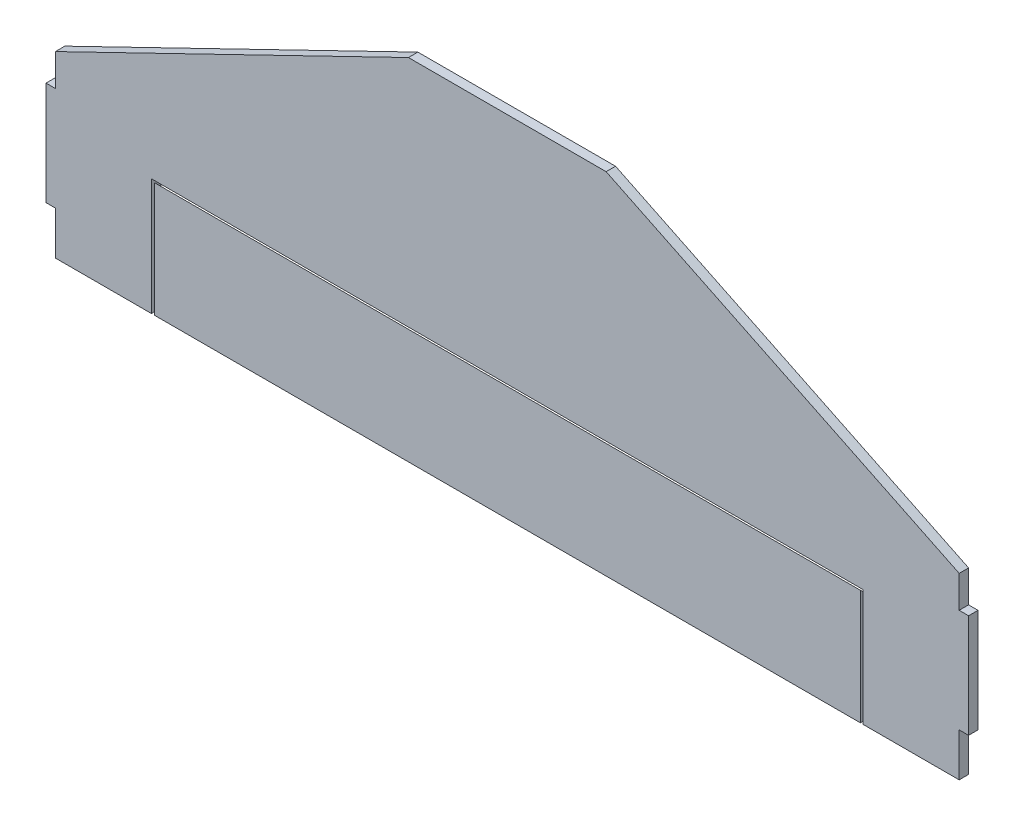
SolidWorks part; units mm, degrees
ref_plane "Ebene vorne" through (0, 0, 0) normal (0, 0, 1) x (1, 0, 0)
ref_plane "Ebene oben" through (0, 0, 0) normal (0, 1, 0) x (1, 0, 0)
ref_plane "Ebene rechts" through (0, 0, 0) normal (1, 0, 0) x (0, 0, -1)
sketch "Skizze1" plane through (0, 0, 0) normal (0, 0, 1) x (1, 0, 0)
  line L0 (0, 0) -> (0, 186) construction
  line L1 (240, 0) -> (-240, 0)
  line L2 (-240, 0) -> (-240, 95)
  line L3 (-240, 95) -> (-52.5, 186)
  line L4 (-52.5, 186) -> (52.5, 186)
  line L5 (240, 0) -> (240, 95)
  line L6 (240, 95) -> (52.5, 186)
  dimension "D1" = 480
  dimension "D2" = 186
  dimension "D3" = 95
  dimension "D4" = 105
extrude "Grundfläche" add sketch "Skizze1" along normal blind 5
sketch "Skizze3" plane through (0, 0, 5) normal (0, 0, 1) x (1, 0, 0)
  line L0 (0, 0) -> (0, 186) construction
  line L1 (52.5, 186) -> (-52.5, 186) construction
  line L2 (240, 0) -> (240, 95) construction
  line L3 (240, 78) -> (245, 78)
  line L4 (240, 78) -> (240, 23)
  line L5 (240, 23) -> (245, 23)
  line L6 (245, 78) -> (245, 23)
  line L7 (-245, 78) -> (-245, 23)
  line L8 (-240, 23) -> (-245, 23)
  line L9 (-240, 78) -> (-240, 23)
  line L10 (-240, 78) -> (-245, 78)
  dimension "D1" = 5
  dimension "D2" = 55
  dimension "D3" = 17
extrude "ZapfenSeitenleitwerk" add sketch "Skizze3" against normal up to surface (5 mm away) up to face at (0, 93.6667, 0)
sketch "Skizze4" plane through (0, 0, 5) normal (0, 0, 1) x (1, 0, 0)
  line L0 (0, 0) -> (0, 62) construction
  line L1 (187.5, 62) -> (-187.5, 62) construction
  line L2 (-187.5, 61) -> (-187.5, 0) construction
  line L3 (-240, 0) -> (240, 0) construction
  line L4 (187.5, 62) -> (187.5, 0) construction
  line L5 (-187.5, 0) -> (-189, 0)
  line L6 (-187.5, 0) -> (-187.5, 61)
  line L7 (-187.5, 62) -> (-189, 62)
  line L8 (-189, 0) -> (-189, 62)
  line L9 (189, 0) -> (189, 62)
  line L10 (187.5, 62) -> (189, 62)
  line L11 (187.5, 0) -> (187.5, 61)
  line L12 (187.5, 0) -> (189, 0)
  line L14 (-187.5, 62) -> (187.5, 62)
  line L16 (-187.5, 61) -> (187.5, 61)
  dimension "D1" = 1.5
  dimension "D2" = 62
  dimension "D3" = 375
  dimension "D4" = 1
extrude "Höhenleitwerk" cut sketch "Skizze4" against normal through all
chamfer "Fase1" distance 5 angle 45 1 edges at (0, 61, 0)
